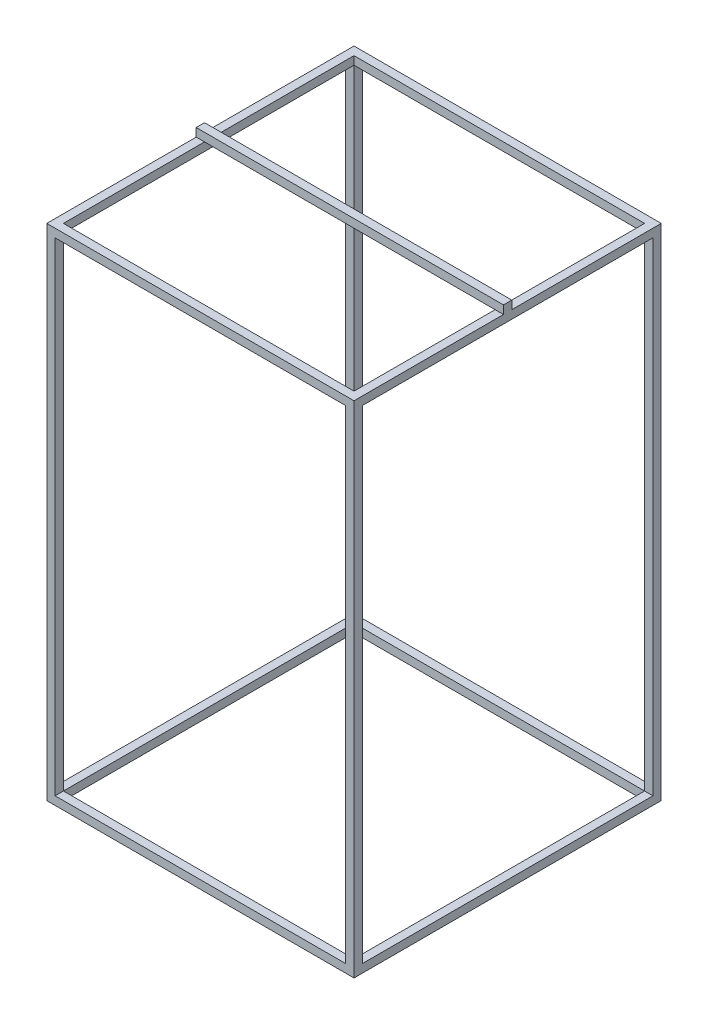
SolidWorks part; units mm, degrees
note: The reader was unsure of these and kept them because the rebuilt part matched: shared geometry of "Sketch2<4>", "Sketch2<5>", "Sketch2<6>".
ref_plane "Front Plane" through (0, 0, 0) normal (0, 0, 1) x (1, 0, 0)
ref_plane "Top Plane" through (0, 0, 0) normal (0, 1, 0) x (1, 0, 0)
ref_plane "Right Plane" through (0, 0, 0) normal (1, 0, 0) x (0, 0, -1)
sketch "Sketch2" plane through (0, 0, 0) normal (0, 1, 0) x (1, 0, 0)
  line L0 (-720.725, 0) -> (720.725, 0) construction
  line L1 (-762, -762) -> (762, -762)
  line L2 (-762, -762) -> (-762, 762)
  line L3 (-762, 762) -> (762, 762)
  line L4 (762, -762) -> (762, 762)
  line L5 (-762, -762) -> (762, 762) construction
  line L6 (-762, 762) -> (762, -762) construction
  line L7 (-720.725, -720.725) -> (720.725, -720.725)
  line L8 (-720.725, -720.725) -> (-720.725, 720.725)
  line L9 (-720.725, 720.725) -> (720.725, 720.725)
  line L10 (720.725, -720.725) -> (720.725, 720.725)
  line L11 (-720.725, -720.725) -> (720.725, 720.725) construction
  line L12 (-720.725, 720.725) -> (720.725, -720.725) construction
  line L13 (762, 762) -> (720.725, 762)
  line L14 (762, 762) -> (762, 720.725)
  line L15 (762, 720.725) -> (720.725, 720.725)
  line L16 (720.725, 762) -> (720.725, 720.725)
  line L17 (0, 720.725) -> (0, -720.725) construction
  line L19 (-762, 762) -> (-720.725, 762)
  line L20 (-762, 762) -> (-762, 720.725)
  line L21 (-762, 720.725) -> (-720.725, 720.725)
  line L22 (-720.725, 762) -> (-720.725, 720.725)
  line L23 (762, -762) -> (720.725, -762)
  line L24 (762, -762) -> (762, -720.725)
  line L25 (762, -720.725) -> (720.725, -720.725)
  line L26 (720.725, -762) -> (720.725, -720.725)
  line L27 (-762, -762) -> (-720.725, -762)
  line L28 (-762, -762) -> (-762, -720.725)
  line L29 (-762, -720.725) -> (-720.725, -720.725)
  line L30 (-720.725, -762) -> (-720.725, -720.725)
  line L31 (-762, -20.6375) -> (762, -20.6375)
  line L32 (-762, -20.6375) -> (-762, 20.6375)
  line L33 (-762, 20.6375) -> (762, 20.6375)
  line L34 (762, -20.6375) -> (762, 20.6375)
  line L35 (-762, -20.6375) -> (762, 20.6375) construction
  line L36 (-762, 20.6375) -> (762, -20.6375) construction
  point P0 (0, 0)
  point P6 (0, 0)
  point P17 (0, 0)
  dimension "D1" = 41.275
  dimension "D2" = 1524
  dimension "D3" = 1524
  dimension "D4" = 41.275
extrude "Boss-Extrude1" add sketch "Sketch2" along normal blind 41.275 contours L3 L16 L15 L4 | L25 L4 L15 L10 | L26 L1 L4 L25 | L30 L1 L26 L7 | L1 L30 L29 L2 | L2 L29 L8 L21
extrude "Boss-Extrude2" add sketch "Sketch2<4>" along normal blind 2438.4 contours L22 L3 L2 L21 | L3 L16 L15 L4 | L26 L1 L4 L25 | L1 L30 L29 L2
sketch "Sketch2<4>" plane through (0, 0, 0) normal (0, 1, 0) x (1, 0, 0) same geometry as "Sketch2"
extrude "Boss-Extrude3" add sketch "Sketch2<5>" along normal blind 41.275 from surface at 2438.4 contours L1 L30 L29 L2 | L22 L3 L2 L21 | L2 L29 L8 L21 | L3 L22 L9 L16 | L3 L16 L15 L4 | L25 L4 L15 L10 | L26 L1 L4 L25 | L30 L1 L26 L7 | L10 L33 L4 L15 | L31 L10 L25 L4 | L2 L33 L8 L21 | L31 L2 L29 L8
sketch "Sketch2<5>" plane through (0, 0, 0) normal (0, 1, 0) x (1, 0, 0) same geometry as "Sketch2"
extrude "Boss-Extrude5" add sketch "Sketch2<6>" along normal blind 41.275 from surface at 2479.675 contours L33 L8 L31 L10 | L33 L10 L31 L4 | L33 L2 L31 L8 starting at face at (0, 2479.675, 0)
sketch "Sketch2<6>" plane through (0, 0, 0) normal (0, 1, 0) x (1, 0, 0) same geometry as "Sketch2"
